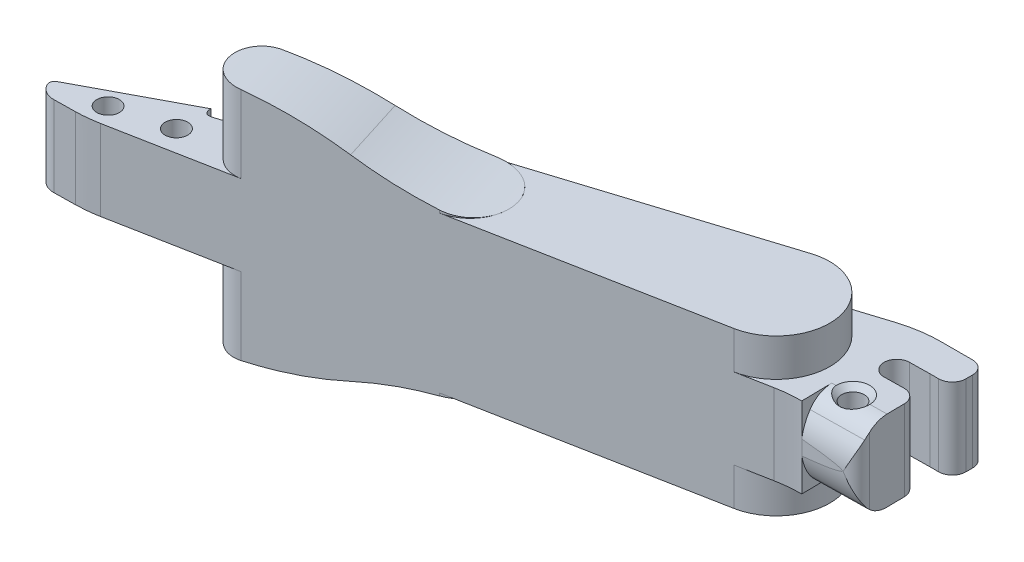
SolidWorks part; units mm, degrees
ref_plane "Front Plane" through (0, 0, 0) normal (0, 0, 1) x (1, 0, 0)
ref_plane "Top Plane" through (0, 0, 0) normal (0, 1, 0) x (1, 0, 0)
ref_plane "Right Plane" through (0, 0, 0) normal (1, 0, 0) x (0, 0, -1)
sketch "Sketch1" plane through (0, 0, 0) normal (0, 1, 0) x (1, 0, 0)
  line L0 (48.6964, -18.3524) -> (-67.0882, -20.1658) construction
  line L1 (14.1015, -12.6258) -> (13.7037, 12.7711) construction
  line L2 (14.1015, -12.6258) -> (13.9026, 0.0727) construction
  line L3 (14.0468, -9.1341) -> (13.9573, -3.4191) construction
  line L4 (13.7584, 9.2794) -> (13.8479, 3.5644) construction
  line L5 (14.1328, -14.6255) -> (14.1997, -18.8927) construction
  line L6 (14.1997, -18.8927) -> (-49.2926, -19.8871) construction
  line L7 (13.9026, 0.0727) -> (-31.9798, -0.6459) construction
  line L8 (-41.6726, -19.7678) -> (14.0468, -9.1341) construction
  line L9 (-49.2926, -19.8871) -> (13.7584, 9.2794) construction
  line L10 (-49.2926, -19.8871) -> (13.7584, 9.2794)
  line L11 (13.9573, -3.4191) -> (-11.5429, -8.2856) construction
  line L12 (-49.2926, -19.8871) -> (-41.6726, -19.7678)
  line L13 (13.8479, 3.5644) -> (-11.5429, -8.2856) construction
  line L14 (-41.6726, -19.7678) -> (14.0468, -9.1341)
  line L15 (14.0468, -9.1341) -> (20.3976, -9.1341)
  line L16 (20.3976, -9.1341) -> (20.3081, -3.4191)
  line L17 (20.3081, -3.4191) -> (13.9573, -3.4191)
  line L18 (-1.5375, -6.3761) -> (13.9573, -3.4191)
  line L19 (-2.3127, -3.9778) -> (13.8479, 3.5644)
  line L20 (13.8479, 3.5644) -> (20.1972, 3.6638)
  line L21 (20.1972, 3.6638) -> (20.1092, 9.2794)
  line L22 (20.1092, 9.2794) -> (13.7584, 9.2794)
  line L23 (16.9338, 9.2794) -> (17.0226, 3.6141) construction
  line L24 (17.1327, -3.4191) -> (17.2222, -9.1341) construction
  line L25 (-24.4831, -12.6085) -> (-6.8076, -4.4321)
  line L26 (-24.4831, -12.6085) -> (-5.1565, -8.9201)
  circle A0 centre (48.6964, 0.6176) radius 18.97 construction
  arc A1 (-2.3127, -3.9778) -> (-1.5375, -6.3761) centre (-1.7756, -5.1287) ccw
  arc A2 (-6.8076, -4.4321) -> (-5.1565, -8.9201) centre (-1.7756, -5.1287) ccw
  circle A3 centre (17.1767, -6.2268) radius 1.0668
  circle A4 centre (16.9778, 6.4716) radius 1.0668
  point P10 (14.0021, -6.2766)
extrude "Boss-Extrude1" add sketch "Sketch1" along normal blind 7.62 contours A1 L19 L20 L21 L22 L10 L12 L14 L15 L16 L17 L18 A4 A3 L25 A2 L26 region at (-17.4499, 0, 5.9895)
fillet "Fillet1" radius 0.635 2 edges at (-5.1565, 3.81, 8.9201) (-6.8076, 3.81, 4.4321)
fillet "Fillet2" radius 0.254 1 edges at (-24.4831, 3.81, 12.6085)
fillet "Fillet3" radius 12.7 1 edges at (13.9573, 3.81, 3.4191)
fillet "Fillet4" radius 6.35 1 edges at (13.7584, 3.81, -9.2794)
fillet "Fillet5" radius 6.35 1 edges at (13.8479, 3.81, -3.5644)
fillet "Fillet6" radius 12.7 1 edges at (14.0468, 3.81, 9.1341)
fillet "Fillet7" radius 1.27 4 edges at (20.3976, 3.81, 9.1341) (20.3081, 3.81, 3.4191) (20.1972, 3.81, -3.6638) (20.1092, 3.81, -9.2794)
chamfer "Chamfer1" distance 0.508 angle 45 4 edges at (17.1767, 0, 7.2936) (16.9778, 0, -5.4048) (17.1767, 7.62, 7.2936) (16.9778, 7.62, -5.4048)
sketch "Sketch2" plane through (0, 7.62, 0) normal (0, 1, 0) x (1, 0, 0)
  line L0 (-49.2926, -19.8871) -> (-36.5926, -12.1327)
  line L1 (-36.5926, -12.1327) -> (-36.5926, -14.0123)
  line L2 (-49.2926, -19.8871) -> (12.49, 8.6926) construction
  line L3 (-49.2926, -19.8871) -> (-36.5926, -14.0123)
  dimension "D1" = 1.8796
  dimension "D2" = 12.7
extrude "Boss-Extrude2" add sketch "Sketch2" against normal up to surface (7.62 mm away) up to face at (17.1767, 0, 7.8016)
sketch "Sketch3" plane through (0, 7.62, 0) normal (0, 1, 0) x (1, 0, 0)
  line L0 (-36.5926, -14.0123) -> (-36.5926, -18.7983) construction
  line L1 (-41.6726, -19.7678) -> (12.8671, -9.3592) construction
  line L2 (-41.6726, -19.7678) -> (-41.6726, -15.2345) construction
  line L3 (-36.5926, -12.1327) -> (-49.2926, -19.8871) construction
  circle A0 centre (17.1767, -6.2268) radius 1.0668 construction
  circle A1 centre (-36.5926, -16.4053) radius 1.0668
  circle A2 centre (-41.6726, -17.5011) radius 1.0668
  dimension "D2" = 2.1336
  dimension "D1" = 54.7241
extrude "Cut-Extrude1" cut sketch "Sketch3" against normal through all
sketch "Sketch4" plane through (0, 7.62, 0) normal (0, 1, 0) x (1, 0, 0)
  line L0 (-36.5926, -14.0123) -> (15.0688, 2.2959)
  line L1 (15.1583, -3.4191) -> (15.0688, 2.2959) construction
  line L2 (15.0688, 2.2959) -> (20.2186, 2.2959)
  line L3 (20.3774, -7.8442) -> (20.3277, -4.6692) construction
  line L4 (20.2186, 2.2959) -> (20.3277, -4.6692)
  line L5 (20.3277, -4.6692) -> (15.1641, -3.784)
  line L6 (15.1583, -3.4191) -> (15.2478, -9.1341) construction
  line L7 (15.1641, -3.784) -> (-17.8143, -14.0123)
  line L8 (-17.8143, -14.0123) -> (-36.5926, -14.0123)
extrude "Boss-Extrude3" add sketch "Sketch4" against normal up to surface (7.62 mm away) up to face at (-36.5926, 0, 17.4721)
sketch "Sketch5" plane through (0, 7.62, 0) normal (0, 1, 0) x (1, 0, 0)
  line L0 (-36.5926, -14.0123) -> (2.8974, -1.5463)
  line L1 (2.8974, -1.5463) -> (12.6185, 2.9906) construction
  line L2 (15.2045, 3.5856) -> (18.9273, 3.6439) construction
  line L3 (20.1773, 4.9337) -> (20.1288, 8.0293) construction
  line L4 (18.8589, 9.2794) -> (15.156, 9.2794) construction
  line L5 (-36.5926, -14.0123) -> (12.49, 8.6926) construction
  line L6 (2.8974, -1.5463) -> (12.6185, 2.9906)
  line L7 (15.2045, 3.5856) -> (18.9273, 3.6439)
  line L8 (20.1773, 4.9337) -> (20.1288, 8.0293)
  line L9 (18.8589, 9.2794) -> (15.156, 9.2794)
  line L10 (-36.5926, -14.0123) -> (12.49, 8.6926)
  arc A0 (15.2045, 3.5856) -> (12.6185, 2.9906) centre (15.304, -2.7636) ccw construction
  arc A1 (18.9273, 3.6439) -> (20.1773, 4.9337) centre (18.9074, 4.9138) ccw construction
  arc A2 (20.1288, 8.0293) -> (18.8589, 9.2794) centre (18.8589, 8.0094) ccw construction
  arc A3 (15.156, 9.2794) -> (12.49, 8.6926) centre (15.156, 2.9294) ccw construction
  arc A4 (15.2045, 3.5856) -> (12.6185, 2.9906) centre (15.304, -2.7636) ccw
  arc A5 (18.9273, 3.6439) -> (20.1773, 4.9337) centre (18.9074, 4.9138) ccw
  arc A6 (20.1288, 8.0293) -> (18.8589, 9.2794) centre (18.8589, 8.0094) ccw
  arc A7 (15.156, 9.2794) -> (12.49, 8.6926) centre (15.156, 2.9294) ccw
extrude "Cut-Extrude2" cut sketch "Sketch5" against normal through all
fillet "Fillet8" radius 12.7 1 edges at (15.0688, 3.81, -2.2959) conic rho 0.5
sketch "Sketch6" plane through (0, 7.62, 0) normal (0, 1, 0) x (1, 0, 0)
  line L0 (20.298, -2.7741) -> (11.1753, -2.917) construction
  line L1 (20.3774, -7.8442) -> (20.2186, 2.2959) construction
  line L2 (20.2186, 2.2959) -> (17.0258, 2.2959) construction
  line L5 (18.9183, 2.2959) -> (20.2186, 2.2959)
  line L6 (20.2186, 2.2959) -> (20.238, 1.0571)
  arc A0 (19.1076, -9.1341) -> (20.3774, -7.8442) centre (19.1076, -7.8641) ccw construction
  arc A1 (19.1076, -9.1341) -> (20.3774, -7.8442) centre (19.1076, -7.8641) ccw
  arc A2 (18.909, 3.5454) -> (20.2186, 2.2959) centre (18.9487, 2.2761) cw construction
  arc A3 (20.238, 1.0571) -> (18.9183, 2.2959) centre (18.9683, 1.0269) ccw
  line M3 (20.2186, 2.2959) -> (17.0258, 2.2959)
  line M13 (20.3774, -7.8442) -> (20.2186, 2.2959)
  dimension "D1" = 1.2495
extrude "Cut-Extrude3" cut sketch "Sketch6" against normal through all and the other way through all contours A3 M13 M3 region at (19.9455, 7.62, -2.0174)
sketch "Sketch7" plane through (0, 7.62, 0) normal (0, 1, 0) x (1, 0, 0)
  line L0 (17.1767, -6.2268) -> (20.3513, -6.1771) construction
  line L1 (20.3774, -7.8442) -> (20.238, 1.0571) construction
  line L2 (20.243, 0.7396) -> (10.66, 0.5895) construction
  line L3 (20.2479, 0.4221) -> (20.3252, -4.5101)
  line L4 (20.238, 1.0571) -> (20.2479, 0.4221) construction
  line L5 (19.0156, -3.2606) -> (17.1106, -3.2904)
  line L6 (19.0677, -0.8543) -> (17.1627, -0.8841)
  arc A0 (20.238, 1.0571) -> (19.0184, 2.2959) centre (18.9683, 1.0269) ccw construction
  arc A1 (20.238, 1.0571) -> (19.0184, 2.2959) centre (18.9683, 1.0269) ccw construction
  arc A2 (20.2479, 0.4221) -> (19.0677, -0.8543) centre (18.978, 0.4125) cw
  arc A3 (19.1076, -9.1341) -> (20.3774, -7.8442) centre (19.1076, -7.8641) ccw construction
  arc A4 (19.1076, -9.1341) -> (20.3774, -7.8442) centre (19.1076, -7.8641) ccw construction
  arc A5 (19.0156, -3.2606) -> (20.3252, -4.5101) centre (19.0553, -4.5299) cw
  arc A7 (17.1106, -3.2904) -> (17.1627, -0.8841) centre (17.1816, -2.0882) cw
  point P19 (20.243, 0.7396)
  dimension "D1" = 0.635
  dimension "D2" = 1.905
  dimension "D3" = 0.0034
extrude "Cut-Extrude4" cut sketch "Sketch7" against normal through all
fillet "Fillet9" radius 0.635 1 edges at (-36.5926, 3.81, 14.0123) conic rho 0.5
fillet "Fillet10" radius 12.7 1 edges at (-41.6726, 3.81, 19.7678) conic rho 0.5
sketch "Sketch9" plane through (0, 7.62, 0) normal (0, 1, 0) x (1, 0, 0)
  line L0 (-35.7664, -13.7515) -> (-35.7664, -18.6406) construction
  line L1 (-40.5913, -19.5614) -> (12.8671, -9.3592) construction
  line L2 (14.0522, -9.1905) -> (14.0522, 1.9434) construction
  line L3 (-35.7664, -16.1961) -> (14.0522, -3.6236) construction
  line L4 (-10.8571, -13.9314) -> (-10.8571, -5.8882) construction
  line L5 (13.2027, 1.7068) -> (-35.7664, -13.7515) construction
  line L6 (-35.7664, -16.1961) -> (-10.8571, -9.9098) construction
  line L7 (-29.4164, -13.7515) -> (-29.4164, -18.6406) construction
  line L8 (-15.9371, -13.9314) -> (-15.9371, -5.8882) construction
  line L9 (-29.4164, -14.5935) -> (-15.9371, -11.1918) construction
  line L10 (-29.5718, -13.9778) -> (-16.0925, -10.5761) construction
  line L11 (-29.261, -15.2092) -> (-15.7817, -11.8075) construction
  line L12 (-5.7771, -13.9314) -> (-5.7771, -5.8882) construction
  line L13 (8.9722, -9.1905) -> (8.9722, 1.9434) construction
  line L14 (-5.7771, -8.6278) -> (8.9722, -4.9056) construction
  line L17 (-29.5718, -13.9778) -> (-15.2443, -9.455) construction
  line L18 (-29.261, -15.2092) -> (-14.503, -12.3927) construction
  line L19 (-29.5718, -13.9778) -> (-15.2443, -9.455)
  line L20 (-29.261, -15.2092) -> (-14.503, -12.3927)
  line L21 (-6.1656, -7.0885) -> (8.5837, -3.3663) construction
  line L22 (-5.3887, -10.167) -> (9.3606, -6.4448) construction
  line L23 (-6.1656, -7.0885) -> (8.5876, -2.4313) construction
  line L24 (-5.3887, -10.167) -> (9.8078, -7.2669) construction
  line L25 (-5.3887, -10.167) -> (9.8078, -7.2669)
  line L26 (-6.1656, -7.0885) -> (8.5876, -2.4313)
  arc A0 (15.2478, -9.1341) -> (12.8671, -9.3592) centre (15.2478, -21.8341) ccw construction
  arc A1 (-29.5718, -13.9778) -> (-29.261, -15.2092) centre (-29.4164, -14.5935) ccw construction
  arc A2 (-15.7817, -11.8075) -> (-16.0925, -10.5761) centre (-15.9371, -11.1918) ccw construction
  arc A5 (-29.5718, -13.9778) -> (-29.261, -15.2092) centre (-29.3803, -14.5844) ccw
  arc A6 (-15.2443, -9.455) -> (-14.503, -12.3927) centre (-14.7875, -10.9021) cw
  arc A7 (-6.1656, -7.0885) -> (-5.3887, -10.167) centre (-5.7771, -8.6278) ccw construction
  arc A8 (9.3606, -6.4448) -> (8.5837, -3.3663) centre (8.9722, -4.9056) ccw construction
  arc A9 (-6.1656, -7.0885) -> (-5.3887, -10.167) centre (-5.6869, -8.605) ccw
  arc A10 (8.5876, -2.4313) -> (9.8078, -7.2669) centre (9.3396, -4.8133) cw
  parabola Q0 (17.0258, 2.2959) -> (13.2027, 1.7068) focus (16.0473, -4.0541) apex (15.0915, 2.1487) construction
  point P21 (-10.8571, -9.9098)
  point P28 (-22.6768, -12.8927)
  point P39 (1.5975, -6.7667)
  dimension "D9" = 0.6361
  dimension "D10" = 1.5175
  dimension "D11" = 1.5902
  dimension "D12" = 7.0885
  dimension "D1" = 25.6903
  dimension "D2" = 6.35
  dimension "D3" = 5.08
  dimension "D4" = 8.0431
  dimension "D5" = 1.27
  dimension "D7" = 5.08
  dimension "D8" = 3.175
  dimension "D13" = 8.5876
  dimension "D6" = 5.08
extrude "Cut-Extrude5" cut sketch "Sketch9" against normal through all
sketch "Sketch10" plane through (20.2496, 0, -0.3171) normal (0.9999, 0, -0.0157) x (-0.0157, 0, -0.9999)
  line L0 (-9.4322, 7.62) -> (-9.4323, 0) construction
  line L1 (-9.4322, 3.81) -> (-3.5578, 3.81) construction
  line L2 (-3.5578, 0) -> (-3.5578, 7.62) construction
  line L3 (-3.5578, 3.81) -> (-3.5578, 7.62) construction
  line L4 (-3.5578, 7.62) -> (-3.5578, 0) construction
  line L5 (-9.4322, 7.62) -> (-3.5578, 7.62) construction
  line L6 (-9.4322, 7.62) -> (-6.495, 3.81) construction
  line L7 (-9.4322, 3.81) -> (-9.4322, 7.62) construction
  line L8 (-9.4322, 7.62) -> (-6.495, 7.62)
  line L9 (-9.4322, 0) -> (-6.495, 3.81) construction
  line L10 (-9.4322, 3.81) -> (-9.4322, 0) construction
  line L12 (-9.4322, 7.62) -> (-11.9722, 7.62)
  line L13 (-11.9722, 7.62) -> (-11.9722, 0)
  line L14 (-11.9722, 0) -> (-6.495, 0)
  arc A0 (-9.4322, 3.81) -> (-8.5792, 6.5136) centre (-4.4618, 3.7282) cw
  arc A1 (-8.5792, 6.5136) -> (-6.495, 7.62) centre (-6.495, 5.1036) cw
  arc A2 (-8.5792, 1.1064) -> (-6.495, 0) centre (-6.495, 2.5164) ccw
  arc A3 (-9.4322, 3.81) -> (-8.5792, 1.1064) centre (-4.4618, 3.8918) ccw
  dimension "D1" = 4.9711
  dimension "D2" = 2.54
extrude "Cut-Extrude7" cut sketch "Sketch10" against normal up to vertex (5.1491 mm away) up to point (15.2478, 7.62, 9.1341)
sketch "Sketch11" plane through (0, 7.62, 0) normal (0, 1, 0) x (1, 0, 0)
  line L0 (-36.5926, -13.1459) -> (-36.5926, -12.1327) construction
  line L2 (-36.5926, -12.1327) -> (-49.2926, -19.8871) construction
  line L3 (-36.5926, -13.1459) -> (-36.5926, -12.1327)
  line L5 (-36.5926, -12.1327) -> (-49.2926, -19.8871)
  line L8 (-49.2926, -19.8871) -> (-36.5926, -13.1459) construction
  line L9 (-49.2926, -19.8871) -> (-36.5926, -13.1459)
extrude "Cut-Extrude8" cut sketch "Sketch11" against normal through all
sketch "Sketch12" plane through (0, 7.62, 0) normal (0, 1, 0) x (1, 0, 0)
  circle A0 centre (-41.6726, -17.5011) radius 1.0668
sketch "Sketch13" plane through (0, 7.62, 0) normal (0, 1, 0) x (1, 0, 0)
  circle A0 centre (-41.6726, -17.5011) radius 1.0668 construction
  circle A1 centre (-41.6726, -17.5011) radius 1.0668
extrude "Boss-Extrude4" add sketch "Sketch13" against normal up to surface (7.62 mm away) up to face at (-21.9008, 0, 12.6971)
sketch "Sketch14" plane through (0, 7.62, 0) normal (0, 1, 0) x (1, 0, 0)
  line L0 (-41.6726, -24.1671) -> (-41.6726, -10.8351) construction
  line L1 (-41.6726, -15.8424) -> (-41.6774, -19.7205) construction
  line L2 (-49.2926, -19.8871) -> (-36.5926, -13.1459) construction
  circle A0 centre (-41.675, -17.7815) radius 1.0668
  circle A1 centre (-36.5926, -16.4053) radius 1.0668 construction
  parabola Q0 (-42.7732, -19.785) -> (-40.5913, -19.5614) focus (-42.3223, -13.4272) apex (-41.6774, -19.7205) construction
  point P4 (-41.6726, -17.5011)
  dimension "D1" = 17.7815
extrude "Cut-Extrude10" cut sketch "Sketch14" against normal through all
sketch "Sketch15" plane through (0, 7.62, 0) normal (0, 1, 0) x (1, 0, 0)
  line L12 (-36.5926, -13.1459) -> (-49.2926, -19.8871)
  line L13 (-49.2926, -19.8871) -> (-42.7732, -19.785)
  line L14 (-40.5913, -19.5614) -> (12.8671, -9.3592)
  line L15 (15.2478, -9.1341) -> (15.2028, -6.2577)
  line L16 (15.2028, -6.2577) -> (15.6021, -6.2514)
  line L17 (18.7513, -6.2021) -> (20.3513, -6.177)
  line L18 (20.3513, -6.177) -> (20.3252, -4.5101)
  line L19 (19.0156, -3.2606) -> (17.1106, -3.2904)
  line L20 (17.1627, -0.8841) -> (19.0677, -0.8543)
  line L21 (20.2479, 0.4221) -> (20.238, 1.0571)
  line L22 (19.0184, 2.2959) -> (17.0258, 2.2959)
  line L23 (13.2027, 1.7068) -> (-35.7664, -13.7515)
  line L24 (-36.5926, -13.1459) -> (-49.2926, -19.8871)
  line L25 (-49.2926, -19.8871) -> (-42.7732, -19.785)
  line L26 (-40.5913, -19.5614) -> (12.8671, -9.3592)
  circle A0 centre (-36.5926, -16.4053) radius 1.0668 construction
  circle A1 centre (-36.5926, -16.4053) radius 1.0668
  circle A2 centre (-41.675, -17.7815) radius 1.0668 construction
  circle A3 centre (-41.675, -17.7815) radius 1.0668
  arc A6 (15.2478, -9.1341) -> (12.8671, -9.3592) centre (15.2478, -21.8341) ccw
  arc A7 (18.7513, -6.2021) -> (15.6021, -6.2514) centre (17.1767, -6.2268) ccw
  arc A8 (20.3252, -4.5101) -> (19.0156, -3.2606) centre (19.0553, -4.5299) ccw
  arc A9 (17.1627, -0.8841) -> (17.1106, -3.2904) centre (17.1816, -2.0882) ccw
  arc A10 (19.0677, -0.8543) -> (20.2479, 0.4221) centre (18.978, 0.4125) ccw
  arc A11 (20.238, 1.0571) -> (19.0184, 2.2959) centre (18.9683, 1.0269) ccw
  parabola Q0 (-35.7664, -13.7515) -> (-36.5926, -13.1459) focus (-36.2751, -13.5791) apex (-36.386, -13.7305) construction
  parabola Q1 (-35.7664, -13.7515) -> (-36.5926, -13.1459) focus (-36.2751, -13.5791) apex (-36.386, -13.7305)
  parabola Q3 (-42.7732, -19.785) -> (-40.5913, -19.5614) focus (-42.3223, -13.4272) apex (-41.6774, -19.7205)
  parabola Q4 (17.0258, 2.2959) -> (13.2027, 1.7068) focus (16.0473, -4.0541) apex (15.0915, 2.1487)
  parabola Q5 (-35.7664, -13.7515) -> (-36.5926, -13.1459) focus (-36.2751, -13.5791) apex (-36.386, -13.7305)
  parabola Q6 (-42.7732, -19.785) -> (-40.5913, -19.5614) focus (-42.3223, -13.4272) apex (-41.6774, -19.7205)
  dimension "D1" = 0
sketch "Sketch16" plane through (0, 0, 0) normal (1, 0, 0) x (0, 0, -1)
  line L0 (-19.8871, 7.62) -> (-19.8871, 0) construction
sketch "Sketch17" plane through (0, 7.62, 0) normal (0, 1, 0) x (1, 0, 0)
  line L0 (-49.4093, -19.889) -> (-44.7718, -19.8163)
  line L1 (-54.1186, -19.9627) -> (-49.4093, -19.889)
  line L2 (-54.1186, -19.9627) -> (-45.433, -16.5067)
  line L6 (-49.2926, -19.8871) -> (-55.9826, -19.9919) construction
  line L7 (-49.2926, -19.8871) -> (-42.7732, -19.785) construction
  arc A0 (-45.433, -16.5067) -> (-44.7718, -19.8163) centre (-44.7987, -18.1008) ccw
  dimension "D1" = 17.526
extrude "Cut-Extrude11" cut sketch "Sketch17" against normal through all
fillet "Fillet11" radius 0.635 1 edges at (-46.4883, 3.81, 18.3986) conic rho 0.5
sketch "Sketch19" plane through (0, 7.62, 0) normal (0, 1, 0) x (1, 0, 0)
  line L0 (17.1106, -3.2904) -> (17.1106, -9.1341) construction
  line L1 (15.2478, -9.1341) -> (19.1076, -9.1341) construction
sketch "Sketch20" plane through (0, 7.62, 0) normal (0, 1, 0) x (1, 0, 0)
  line L0 (17.1106, -3.2904) -> (17.1777, -9.1341) construction
  line L1 (15.2478, -9.1341) -> (19.1076, -9.1341) construction
  line L2 (17.1627, -0.8841) -> (17.1627, 2.2959) construction
  line L3 (19.0184, 2.2959) -> (17.0258, 2.2959) construction
sketch "Sketch21" plane through (0, 7.62, 0) normal (0, 1, 0) x (1, 0, 0)
  line L0 (20.243, 0.7396) -> (20.3513, -6.177) construction
  line L1 (20.2479, 0.4221) -> (20.238, 1.0571) construction
  line L2 (15.9776, -2.0621) -> (20.2868, -2.0621) construction
  line L3 (20.243, 0.7396) -> (22.148, 0.7396) construction
  line L5 (19.0184, 2.2959) -> (20.9147, 2.2959)
  line L6 (22.1527, 0.4519) -> (22.1428, 1.0869)
  line L7 (22.1527, 0.4519) -> (22.1428, 1.0869)
  line L8 (19.0677, -0.8543) -> (20.8667, -0.8543)
  line L9 (19.0184, 2.2959) -> (19.0677, -0.8543)
  arc A0 (17.1627, -0.8841) -> (17.1106, -3.2904) centre (17.1816, -2.0882) ccw construction
  arc A2 (20.9147, 2.2959) -> (22.1428, 1.0869) centre (20.9147, 1.0677) cw
  arc A3 (22.1527, 0.4519) -> (20.8667, -0.8543) centre (20.8667, 0.4318) cw
  dimension "D1" = 1.905
  dimension "D2" = 1.905
extrude "Boss-Extrude5" add sketch "Sketch21" against normal up to surface (7.62 mm away) up to face at (-41.675, 0, 18.8483)
sketch "Sketch22" plane through (0, 0, 0) normal (0, -1, 0) x (1, 0, 0)
  line L0 (9.6618, 9.9709) -> (-29.4658, 17.4382)
  line L1 (7.1937, 0.19) -> (-30.7923, 12.1813)
  line L2 (9.8078, 7.2669) -> (-5.3887, 10.167)
  line L3 (8.5876, 2.4313) -> (-6.1656, 7.0885)
  line L4 (-14.503, 12.3927) -> (-29.261, 15.2092)
  line L5 (-29.5718, 13.9778) -> (-15.2443, 9.455)
  arc A0 (9.6618, 9.9709) -> (7.1937, 0.19) centre (8.7146, 5.0081) cw
  arc A1 (-29.4658, 17.4382) -> (-30.7923, 12.1813) centre (-29.9749, 14.7708) ccw
  arc A2 (-5.3887, 10.167) -> (-6.1656, 7.0885) centre (-5.6869, 8.605) ccw
  arc A3 (9.8078, 7.2669) -> (8.5876, 2.4313) centre (9.3396, 4.8133) cw
  arc A4 (-14.503, 12.3927) -> (-15.2443, 9.455) centre (-14.7875, 10.9021) cw
  arc A7 (-29.261, 15.2092) -> (-29.5718, 13.9778) centre (-29.3803, 14.5844) ccw
extrude "Boss-Extrude6" add sketch "Sketch22" along normal blind 3.556
sketch "Sketch23" plane through (0, 7.62, 0) normal (0, 1, 0) x (1, 0, 0)
  line L0 (-15.2443, -9.455) -> (-29.5718, -13.9778) construction
  line L1 (-29.261, -15.2092) -> (-14.503, -12.3927) construction
  line L2 (-29.4658, -17.4382) -> (9.6618, -9.9709)
  line L3 (7.1937, -0.19) -> (-30.7923, -12.1813)
  line L4 (-29.4658, -17.4382) -> (9.6618, -9.9709)
  line L5 (7.1937, -0.19) -> (-30.7923, -12.1813)
  line L6 (8.5876, -2.4313) -> (-6.1656, -7.0885) construction
  line L7 (-5.3887, -10.167) -> (9.8078, -7.2669) construction
  line L8 (-15.2443, -9.455) -> (-29.5718, -13.9778)
  line L9 (-29.261, -15.2092) -> (-14.503, -12.3927)
  line L10 (8.5876, -2.4313) -> (-6.1656, -7.0885)
  line L11 (-5.3887, -10.167) -> (9.8078, -7.2669)
  arc A0 (-29.5718, -13.9778) -> (-29.261, -15.2092) centre (-29.3803, -14.5844) ccw construction
  arc A1 (-14.503, -12.3927) -> (-15.2443, -9.455) centre (-14.7875, -10.9021) ccw construction
  arc A2 (9.6618, -9.9709) -> (7.1937, -0.19) centre (8.7146, -5.0081) ccw
  arc A3 (-30.7923, -12.1813) -> (-29.4658, -17.4382) centre (-29.9749, -14.7708) ccw
  arc A4 (9.6618, -9.9709) -> (7.1937, -0.19) centre (8.7146, -5.0081) ccw
  arc A5 (-30.7923, -12.1813) -> (-29.4658, -17.4382) centre (-29.9749, -14.7708) ccw
  arc A6 (-6.1656, -7.0885) -> (-5.3887, -10.167) centre (-5.6869, -8.605) ccw construction
  arc A7 (9.8078, -7.2669) -> (8.5876, -2.4313) centre (9.3396, -4.8133) ccw construction
  arc A8 (-29.5718, -13.9778) -> (-29.261, -15.2092) centre (-29.3803, -14.5844) ccw
  arc A9 (-14.503, -12.3927) -> (-15.2443, -9.455) centre (-14.7875, -10.9021) ccw
  arc A10 (-6.1656, -7.0885) -> (-5.3887, -10.167) centre (-5.6869, -8.605) ccw
  arc A11 (9.8078, -7.2669) -> (8.5876, -2.4313) centre (9.3396, -4.8133) ccw
  dimension "D1" = 0
extrude "Boss-Extrude7" add sketch "Sketch23" along normal blind 3.556
sketch "Sketch24" plane through (0, -3.556, 0) normal (0, -1, 0) x (1, 0, 0)
  line L0 (-14.503, 12.3927) -> (-29.261, 15.2092) construction
  line L1 (-29.5718, 13.9778) -> (-15.2443, 9.455) construction
  line L2 (-6.1656, 7.0885) -> (8.5876, 2.4313) construction
  line L3 (9.8078, 7.2669) -> (-5.3887, 10.167) construction
  line L4 (-14.503, 12.3927) -> (-29.261, 15.2092)
  line L5 (-29.5718, 13.9778) -> (-15.2443, 9.455)
  line L6 (-6.1656, 7.0885) -> (8.5876, 2.4313)
  line L7 (9.8078, 7.2669) -> (-5.3887, 10.167)
  arc A0 (-29.261, 15.2092) -> (-29.5718, 13.9778) centre (-29.3803, 14.5844) ccw construction
  arc A1 (-15.2443, 9.455) -> (-14.503, 12.3927) centre (-14.7875, 10.9021) ccw construction
  arc A2 (8.5876, 2.4313) -> (9.8078, 7.2669) centre (9.3396, 4.8133) ccw construction
  arc A3 (-5.3887, 10.167) -> (-6.1656, 7.0885) centre (-5.6869, 8.605) ccw construction
  arc A4 (-29.261, 15.2092) -> (-29.5718, 13.9778) centre (-29.3803, 14.5844) ccw
  arc A5 (-15.2443, 9.455) -> (-14.503, 12.3927) centre (-14.7875, 10.9021) ccw
  arc A6 (8.5876, 2.4313) -> (9.8078, 7.2669) centre (9.3396, 4.8133) ccw
  arc A7 (-5.3887, 10.167) -> (-6.1656, 7.0885) centre (-5.6869, 8.605) ccw
extrude "Boss-Extrude8" add sketch "Sketch24" against normal up to surface (14.732 mm away) up to face at (-10.1739, 11.176, 9.7743)
ref_plane "Plane2" through (-33.2794, 0, 0) normal (1, 0, 0) x (0, 0, -1)
sketch "Sketch25" plane through (-33.2794, 0, 0) normal (1, 0, 0) x (0, 0, -1)
  line L0 (-12.1813, 7.62) -> (-17.4863, 11.176) construction
  line L1 (-17.4863, 11.176) -> (-12.1813, 11.176) construction
  line L2 (-12.1813, 11.176) -> (-12.1813, 7.62) construction
  line L3 (-19.785, 3.81) -> (2.2959, 3.81) construction
  line L4 (-19.785, 0) -> (-19.785, 7.62) construction
  line L5 (2.2959, 0) -> (2.2959, 7.62) construction
  line L6 (-17.4863, -3.556) -> (-12.1813, -3.556) construction
  line L7 (-12.1813, -3.556) -> (-12.1813, 0) construction
  line L8 (-12.1813, 0) -> (-17.4863, -3.556) construction
  line L9 (-11.5463, 11.176) -> (-11.5463, 7.62) construction
  line L10 (-17.4382, 11.176) -> (-9.9709, 11.176) construction
  line L11 (-17.4863, 11.176) -> (-18.1213, 11.176) construction
  line L12 (-18.1213, 11.176) -> (-11.5463, 7.62) construction
  line L13 (-18.1213, 11.176) -> (-11.5463, 11.176) construction
  line L14 (-17.4863, -3.556) -> (-18.1213, -3.556) construction
  line L15 (-12.1813, -3.556) -> (-12.1813, 0) construction
  line L16 (-17.4863, -3.556) -> (-12.1813, -3.556) construction
  line L17 (-12.1813, 0) -> (-17.4863, -3.556) construction
  line L18 (-18.1213, -3.556) -> (-11.5463, -3.556) construction
  line L19 (-18.1213, -3.556) -> (-11.5463, 0) construction
  line L20 (-11.5463, -3.556) -> (-11.5463, 0) construction
  line L21 (-14.8338, 9.398) -> (-10.5989, 6.5593)
  line L22 (-10.5989, 6.5593) -> (-10.5989, 12.2367)
  line L23 (-10.5989, 12.2367) -> (-19.0687, 12.2367)
  line L24 (-14.8338, 9.398) -> (-19.0687, 12.2367)
  line L25 (-14.8338, -1.778) -> (-10.5989, 1.0607)
  line L26 (-14.8338, -1.778) -> (-19.0687, -4.6167)
  line L27 (-10.5989, -4.6167) -> (-19.0687, -4.6167)
  line L28 (-10.5989, 1.0607) -> (-10.5989, -4.6167)
  dimension "D1" = 0.635
  dimension "D2" = 0.635
  dimension "D3" = 1.905
  dimension "D4" = 1.905
ref_plane "Plane3" through (14.0522, 0, 0) normal (1, 0, 0) x (0, 0, -1)
sketch "Sketch26" plane through (14.0522, 0, 0) normal (1, 0, 0) x (0, 0, -1)
  line L0 (-9.9709, 11.176) -> (0.0443, 7.62) construction
  line L1 (0.0443, 7.62) -> (0.0443, 11.176) construction
  line L2 (0.4519, 7.62) -> (-0.8543, 7.62) construction
  line L3 (0.0443, 7.62) -> (0.0443, 11.176) construction
  line L4 (0.0443, 11.176) -> (-9.9709, 11.176) construction
  line L5 (-19.785, 3.81) -> (2.2959, 3.81) construction
  line L6 (-19.785, 0) -> (-19.785, 7.62) construction
  line L7 (2.2959, 0) -> (2.2959, 7.62) construction
  line L8 (0.0443, 0) -> (0.0443, -3.556) construction
  line L9 (-9.9709, -3.556) -> (0.0443, 0) construction
  line L10 (0.0443, -3.556) -> (-9.9709, -3.556) construction
  line L11 (-9.9709, 11.176) -> (-10.6059, 11.176) construction
  line L12 (-17.4382, 11.176) -> (-9.9709, 11.176) construction
  line L13 (0.0443, 7.62) -> (1.9493, 7.62) construction
  line L14 (2.2959, 7.62) -> (1.0869, 7.62) construction
  line L15 (-10.6059, 11.176) -> (1.9493, 11.176) construction
  line L16 (1.9493, 11.176) -> (1.9493, 7.62) construction
  line L17 (-10.6059, 11.176) -> (1.9493, 7.62) construction
  line L18 (0.0443, 0) -> (1.9493, 0) construction
  line L19 (-9.9709, -3.556) -> (-10.6059, -3.556) construction
  line L20 (0.0443, -3.556) -> (-9.9709, -3.556) construction
  line L21 (0.0443, 0) -> (0.0443, -3.556) construction
  line L22 (-9.9709, -3.556) -> (0.0443, 0) construction
  line L23 (-10.6059, -3.556) -> (1.9493, 0) construction
  line L24 (1.9493, -3.556) -> (1.9493, 0) construction
  line L25 (-10.6059, -3.556) -> (1.9493, -3.556) construction
  line L26 (-4.3283, 9.398) -> (5.0042, 6.7548)
  line L27 (-4.3283, 9.398) -> (-13.6608, 12.0412)
  line L28 (-13.6608, 12.0412) -> (5.0042, 12.0412)
  line L29 (5.0042, 12.0412) -> (5.0042, 6.7548)
  line L30 (-13.6608, -4.4212) -> (5.0042, -4.4212)
  line L31 (-4.3283, -1.778) -> (-13.6608, -4.4212)
  line L32 (-4.3283, -1.778) -> (5.0042, 0.8652)
  line L33 (5.0042, -4.4212) -> (5.0042, 0.8652)
  dimension "D1" = 0.635
  dimension "D2" = 1.905
  dimension "D3" = 3.175
  dimension "D4" = 3.175
sketch "Sketch27" plane through (-33.2794, 0, 0) normal (1, 0, 0) x (0, 0, -1)
  line L0 (-17.4382, 11.176) -> (0.0443, 7.62)
  line L1 (0.0443, 7.62) -> (6.9689, 6.2115)
  line L2 (-17.4382, 11.176) -> (-23.444, 12.3976)
  line L3 (-23.444, 12.3976) -> (6.9689, 12.3976)
  line L4 (6.9689, 12.3976) -> (6.9689, 6.2115)
  line L5 (2.2959, 3.81) -> (-19.785, 3.81) construction
  line L6 (2.2959, 0) -> (2.2959, 7.62) construction
  line L7 (-19.785, 0) -> (-19.785, 7.62) construction
  line L8 (-23.444, -4.7776) -> (6.9689, -4.7776)
  line L9 (-17.4382, -3.556) -> (-23.444, -4.7776)
  line L10 (-17.4382, -3.556) -> (0.0443, 0)
  line L11 (0.0443, 0) -> (6.9689, 1.4085)
  line L12 (6.9689, -4.7776) -> (6.9689, 1.4085)
ref_plane "Plane4" through (6.718, 0, -1.6952) normal (0.9696, 0, -0.2447) x (-0.2447, 0, -0.9696)
sketch "Sketch29" plane through (6.718, 0, -1.6952) normal (0.9696, 0, -0.2447) x (-0.2447, 0, -0.9696)
  line L0 (-12.0405, 11.176) -> (-1.9395, 7.62)
  line L1 (-1.9395, 0) -> (-12.0405, -3.556)
  line L2 (-12.0405, -3.556) -> (-1.9356, -3.556)
  line L3 (-1.9356, -3.556) -> (-1.9395, 0)
  line L4 (-1.9395, 7.62) -> (-1.9443, 11.176)
  line L5 (-1.9443, 11.176) -> (-12.0405, 11.176)
ref_plane "Plane5" through (11.9037, 0, -3.0037) normal (0.9696, 0, -0.2447) x (-0.2447, 0, -0.9696)
sketch "Sketch30" plane through (11.9037, 0, -3.0037) normal (0.9696, 0, -0.2447) x (-0.2447, 0, -0.9696)
  line L0 (-1.9443, 11.176) -> (-12.0405, 11.176) construction
  line L2 (-12.0405, 11.176) -> (-1.9395, 7.62) construction
  line L3 (-12.0405, -3.556) -> (-1.9356, -3.556) construction
  line L5 (-1.9395, 0) -> (-12.0405, -3.556) construction
  line L6 (-1.9443, 11.176) -> (-12.0405, 11.176)
  line L8 (-12.0405, 11.176) -> (-1.9395, 7.62)
  line L9 (-12.0405, -3.556) -> (-1.9356, -3.556)
  line L11 (-1.9395, 0) -> (-12.0405, -3.556)
  line L12 (-1.9395, 0) -> (8.883, 3.81)
  line L13 (-1.9395, 7.62) -> (8.883, 3.81)
  line L14 (-1.9443, 11.176) -> (8.883, 11.176)
  line L15 (8.883, 11.176) -> (8.883, 3.81)
  line L16 (8.883, 3.81) -> (8.883, -3.556)
  line L17 (8.883, -3.556) -> (-1.9356, -3.556)
ref_plane "Plane6" through (-31.8388, 0, 8.0341) normal (-0.9696, 0, 0.2447) x (0.2447, 0, 0.9696)
ref_plane "Plane7" through (-34.3176, 0, 8.6596) normal (-0.9696, 0, 0.2447) x (0.2447, 0, 0.9696)
sketch "Sketch32" plane through (-34.3176, 0, 8.6596) normal (-0.9696, 0, 0.2447) x (0.2447, 0, 0.9696)
  line L0 (4.2772, 7.62) -> (9.6989, 11.176)
  line L1 (9.6989, 11.176) -> (4.2772, 11.176)
  line L4 (4.2772, -3.556) -> (9.6989, -3.556)
  line L5 (9.6989, -3.556) -> (4.2772, 0)
  line L6 (4.2772, 7.62) -> (-1.5317, 3.81)
  line L7 (4.2772, 0) -> (-1.5317, 3.81)
  line L8 (-1.5317, 3.81) -> (-1.5317, 11.176)
  line L9 (1.9443, 11.176) -> (-8.883, 11.176) construction
  line L10 (-1.5317, 11.176) -> (4.2772, 11.176)
  line L11 (-1.5317, 3.81) -> (-1.5317, -3.556)
  line L12 (-8.883, -3.556) -> (1.9356, -3.556) construction
  line L13 (-1.5317, -3.556) -> (4.2772, -3.556)
  dimension "D1" = 0
sketch "Sketch33" plane through (-34.3176, 0, 8.6596) normal (-0.9696, 0, 0.2447) x (0.2447, 0, 0.9696)
  line L0 (-1.5317, 3.81) -> (-1.5317, -3.556)
  line L1 (-1.5317, -3.556) -> (9.6989, -3.556)
  line L2 (9.6989, -3.556) -> (-1.5317, 3.81)
  line L3 (-1.5317, 3.81) -> (-1.5317, 11.176)
  line L4 (-1.5317, 11.176) -> (9.6989, 11.176)
  line L5 (9.6989, 11.176) -> (-1.5317, 3.81)
sketch "Sketch34" plane through (11.9037, 0, -3.0037) normal (0.9696, 0, -0.2447) x (-0.2447, 0, -0.9696)
  line L0 (8.883, 3.81) -> (-12.0405, -3.556)
  line L1 (-12.0405, -3.556) -> (8.883, -3.556)
  line L2 (8.883, -3.556) -> (8.883, 3.81)
  line L3 (8.883, 3.81) -> (8.883, 11.176)
  line L4 (8.883, 11.176) -> (-12.0405, 11.176)
  line L5 (-12.0405, 11.176) -> (8.883, 3.81)
sketch "Sketch35" plane through (0, 11.176, 0) normal (0, 1, 0) x (1, 0, 0)
  line L0 (7.1937, -0.19) -> (-30.7923, -12.1813) construction
  line L1 (-15.4967, -7.3529) -> (-30.7923, -12.1813)
  line L2 (-13.7106, -14.4314) -> (-29.4658, -17.4382)
  arc A0 (-29.4658, -17.4382) -> (-30.7923, -12.1813) centre (-29.9749, -14.7708) cw
  arc A1 (-15.4967, -7.3529) -> (-13.7106, -14.4314) centre (-14.396, -10.8397) cw
  arc A2 (-13.7106, -14.4314) -> (-15.4967, -7.3529) centre (-14.396, -10.8397) ccw construction
extrude "Boss-Extrude9" add sketch "Sketch35" along normal blind 3.81
sketch "Sketch36" plane through (0, -3.556, 0) normal (0, -1, 0) x (1, 0, 0)
  line L2 (-13.7106, 14.4314) -> (-29.4658, 17.4382)
  line L3 (-30.7923, 12.1813) -> (-15.4967, 7.3529)
  line L4 (-13.7106, 14.4314) -> (-29.4658, 17.4382)
  line L5 (-30.7923, 12.1813) -> (-15.4967, 7.3529)
  arc A2 (-29.4658, 17.4382) -> (-30.7923, 12.1813) centre (-29.9749, 14.7708) ccw
  arc A3 (-15.4967, 7.3529) -> (-13.7106, 14.4314) centre (-14.396, 10.8397) ccw
  arc A4 (-29.4658, 17.4382) -> (-30.7923, 12.1813) centre (-29.9749, 14.7708) ccw
  arc A5 (-15.4967, 7.3529) -> (-13.7106, 14.4314) centre (-14.396, 10.8397) ccw
  dimension "D1" = 0
extrude "Boss-Extrude10" add sketch "Sketch36" along normal blind 3.81
sketch "Sketch37" plane through (0.7065, 0, 2.2379) normal (-0.301, 0, -0.9536) x (-0.9536, 0, 0.301)
  line L0 (13.3349, -3.556) -> (35.7464, -7.366) construction
  line L1 (33.0309, -7.366) -> (16.9914, -7.366) construction
  line L2 (16.9914, -3.556) -> (-6.8028, -3.556) construction
  line L3 (49.8608, 3.81) -> (13.3349, 3.81) construction
  line L4 (49.8608, 0) -> (49.8608, 7.62) construction
  line L5 (35.7464, -7.366) -> (13.3349, -7.366) construction
  line L6 (13.3349, -7.366) -> (13.3349, -3.556) construction
  line L7 (35.7464, -7.366) -> (13.3349, -7.366)
  line L8 (13.3349, -7.366) -> (13.3349, -3.556)
  line L9 (13.3349, 11.176) -> (13.3349, 14.986)
  line L10 (13.3349, 14.986) -> (35.7464, 14.986)
  arc A0 (13.3349, -3.556) -> (24.5407, -5.461) centre (13.3349, -37.4664) cw
  arc A1 (24.5407, -5.461) -> (35.7464, -7.366) centre (35.7464, 26.5444) ccw
  arc A2 (24.5407, 13.081) -> (35.7464, 14.986) centre (35.7464, -18.9244) cw
  arc A3 (13.3349, 11.176) -> (24.5407, 13.081) centre (13.3349, 45.0864) ccw
extrude "Cut-Extrude14" cut sketch "Sketch37" against normal through all both and the other way through all
sketch "Sketch38" plane through (0, 7.62, 0) normal (0, 1, 0) x (1, 0, 0)
  line L0 (20.3513, -6.177) -> (20.2186, 2.2959) construction
  line L1 (20.9147, 2.2959) -> (17.0258, 2.2959) construction
  line L2 (20.2186, 2.2959) -> (20.2679, -0.8543) construction
  line L3 (19.0677, -0.8543) -> (20.8667, -0.8543) construction
  line L4 (20.2433, 0.7208) -> (22.1477, 0.7507) construction
  line L5 (21.1955, 0.4182) -> (21.1955, 1.0533)
  line L6 (22.1527, 0.4519) -> (22.1428, 1.0869) construction
  line L7 (19.9095, -0.8543) -> (20.8667, -0.8543)
  line L8 (22.1527, 0.4519) -> (22.1428, 1.0869)
  line L9 (20.9147, 2.2959) -> (19.9673, 2.2959)
  arc A0 (19.9673, 2.2959) -> (21.1955, 1.0533) centre (19.9673, 1.0677) cw
  arc A1 (21.1955, 0.4182) -> (19.9095, -0.8543) centre (19.9095, 0.4318) cw
  arc A2 (20.8667, -0.8543) -> (22.1527, 0.4519) centre (20.8667, 0.4318) ccw construction
  arc A3 (22.1428, 1.0869) -> (20.9147, 2.2959) centre (20.9147, 1.0677) ccw construction
  arc A4 (20.8667, -0.8543) -> (22.1527, 0.4519) centre (20.8667, 0.4318) ccw
  arc A5 (22.1428, 1.0869) -> (20.9147, 2.2959) centre (20.9147, 1.0677) ccw
  point P13 (21.1955, 0.7357)
extrude "Cut-Extrude15" cut sketch "Sketch38" against normal through all both and the other way through all
